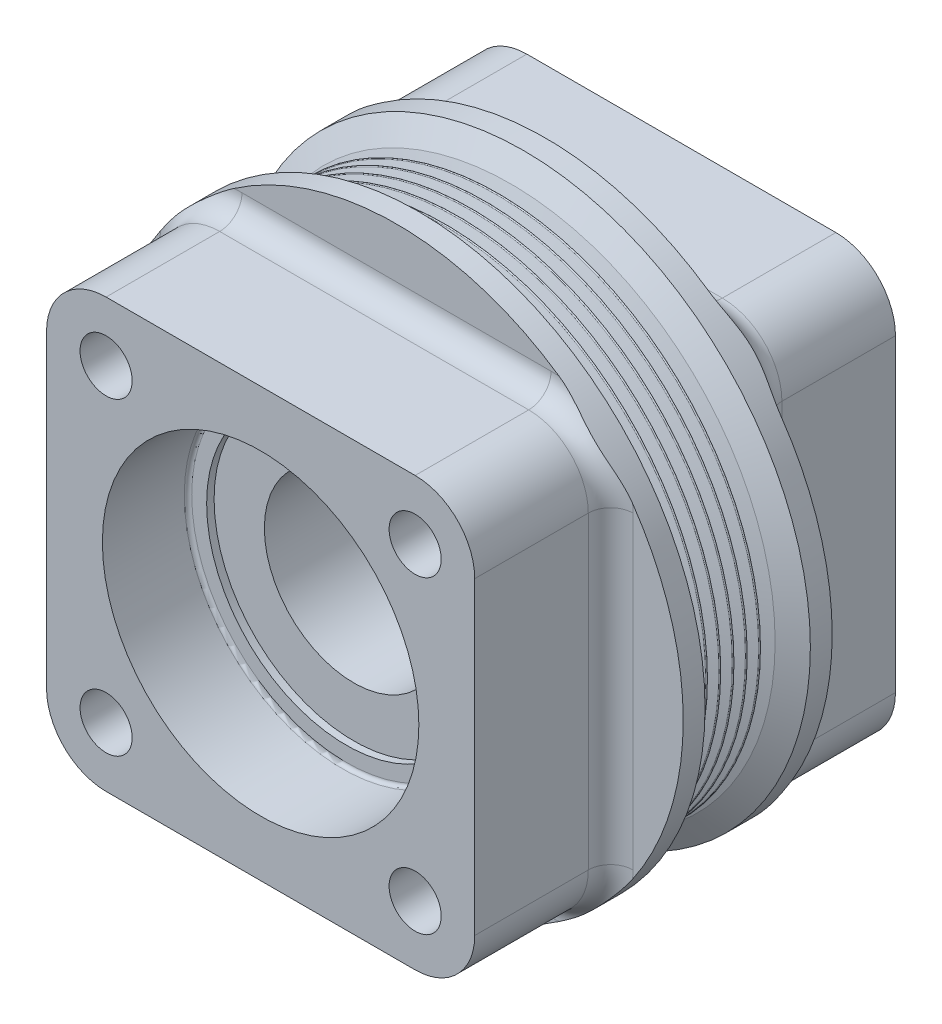
SolidWorks part; units mm, degrees
material "AISI 4340 Aço recozido"
ref_plane "Plano frontal" through (0, 0, 0) normal (0, 0, 1) x (1, 0, 0)
ref_plane "Plano superior" through (0, 0, 0) normal (0, 1, 0) x (1, 0, 0)
ref_plane "Plano direito" through (0, 0, 0) normal (1, 0, 0) x (0, 0, -1)
sketch "Esboço2" plane through (0, 0, 0) normal (0, 0, 1) x (1, 0, 0)
  line L1 (-41.5, -57.5) -> (41.5, -57.5)
  line L2 (-57.5, -41.5) -> (-57.5, 41.5)
  line L3 (-41.5, 57.5) -> (41.5, 57.5)
  line L4 (57.5, -41.5) -> (57.5, 41.5)
  line L5 (-57.5, -57.5) -> (57.5, 57.5) construction
  line L6 (-57.5, 57.5) -> (57.5, -57.5) construction
  arc A0 (-41.5, -57.5) -> (-57.5, -41.5) centre (-41.5, -41.5) cw
  arc A1 (41.5, -57.5) -> (57.5, -41.5) centre (41.5, -41.5) ccw
  arc A2 (41.5, 57.5) -> (57.5, 41.5) centre (41.5, 41.5) cw
  arc A3 (-57.5, 41.5) -> (-41.5, 57.5) centre (-41.5, 41.5) cw
  circle A4 centre (0, 0) radius 42.5
  circle A5 centre (0, 0) radius 25
  point P0 (0, 0)
  dimension "D2" = 16
  dimension "D3" = 85
  dimension "D4" = 50
  dimension "D1" = 115
sketch "Esboço3" plane through (0, 0, 0) normal (1, 0, 0) x (0, 0, -1)
  line L0 (20, 0) -> (20, 77)
  line L1 (20, 77) -> (14.1441, 77)
  line L3 (8.4302, 67.4004) -> (7.3549, 70.3546)
  line L4 (6.8851, 70.3546) -> (5.8098, 67.4004)
  line L5 (4.8702, 67.4004) -> (3.7949, 70.3546)
  line L6 (3.3251, 70.3546) -> (2.2498, 67.4004)
  line L7 (1.3102, 67.4004) -> (0.2349, 70.3546)
  line L8 (-0.2349, 70.3546) -> (-1.3102, 67.4004)
  line L9 (-2.2498, 67.4004) -> (-3.3251, 70.3546)
  line L10 (-3.7949, 70.3546) -> (-4.8702, 67.4004)
  line L11 (-5.8098, 67.4004) -> (-6.8851, 70.3546)
  line L12 (-7.3549, 70.3546) -> (-8.4302, 67.4004)
  line L14 (-14.1441, 77) -> (-20, 77)
  line L15 (-20, 77) -> (-20, 0)
  line L16 (-20, 0) -> (20, 0)
  line L17 (-10.68, 71) -> (10.68, 71) construction
  line L18 (-20, 77) -> (-20, 200)
  line L19 (0, 0) -> (51.063, 0) construction
  line L20 (-9.3698, 67.4004) -> (-10.68, 71)
  line L21 (-10.68, 71) -> (-14.1441, 77)
  line L22 (9.3698, 67.4004) -> (10.68, 71)
  line L23 (10.68, 71) -> (14.1441, 77)
  line L24 (-20, 200) -> (20, 200)
  line L25 (14.1441, 77) -> (20, 87.1427)
  line L26 (20, 87.1427) -> (20, 77)
  line L27 (-14.1441, 77) -> (-20, 87.1427)
  line L28 (-20, 87.1427) -> (-20, 77)
  line L29 (20, 200) -> (20, 77)
  line L30 (20, 77) -> (75, 77)
  line L31 (75, 77) -> (75, 127)
  line L32 (75, 127) -> (-75, 127)
  line L33 (-75, 127) -> (-75, 77)
  line L34 (-75, 77) -> (-20, 77)
  arc A0 (-6.8851, 70.3546) -> (-7.3549, 70.3546) centre (-7.12, 70.269) ccw
  arc A1 (-3.3251, 70.3546) -> (-3.7949, 70.3546) centre (-3.56, 70.269) ccw
  arc A2 (0.2349, 70.3546) -> (-0.2349, 70.3546) centre (0, 70.269) ccw
  arc A3 (3.7949, 70.3546) -> (3.3251, 70.3546) centre (3.56, 70.269) ccw
  arc A4 (7.3549, 70.3546) -> (6.8851, 70.3546) centre (7.12, 70.269) ccw
  arc A5 (9.3698, 67.4004) -> (8.4302, 67.4004) centre (8.9, 67.5714) cw
  arc A6 (5.8098, 67.4004) -> (4.8702, 67.4004) centre (5.34, 67.5714) cw
  arc A7 (2.2498, 67.4004) -> (1.3102, 67.4004) centre (1.78, 67.5714) cw
  arc A8 (-1.3102, 67.4004) -> (-2.2498, 67.4004) centre (-1.78, 67.5714) cw
  arc A9 (-4.8702, 67.4004) -> (-5.8098, 67.4004) centre (-5.34, 67.5714) cw
  arc A10 (-8.4302, 67.4004) -> (-9.3698, 67.4004) centre (-8.9, 67.5714) cw
  point P2 (-7.12, 71)
  point P24 (-7.12, 71)
  point P27 (0, 0)
  point P32 (0, 127)
  point P36 (-7.12, 71)
  point P39 (-3.56, 71)
  point P42 (0, 71)
  point P45 (3.56, 71)
  point P48 (7.12, 71)
  point P54 (5.34, 66.1095)
  point P57 (1.78, 66.1095)
  point P60 (-1.78, 66.1095)
  point P63 (-5.34, 66.1095)
  dimension "D1" = 0.5
  dimension "D2" = 0.25
  dimension "D3" = 40
  dimension "D4" = 40
  dimension "D5" = 20
  dimension "D6" = 3.56
  dimension "D7" = 60
  dimension "D8" = 30
  dimension "D9" = 142
  dimension "D10" = 6
  dimension "D11" = 200
  dimension "D12" = 150
  dimension "D13" = 50
extrude "EXTRUSÃO QUADRADO" add sketch "Esboço2" along normal mid plane 113 contours L3 A2 L4 A1 L1 A0 L2 A3
revolve "REVOLUÇÃO POLIA" add sketch "Esboço3" angle 360 about L16 region at (0, 36.1147, 0)
revolve "CORTE REVOLUÇÃO POLIA" cut sketch "Esboço3<4>" angle 360 about L19 region at (0, 80.3809, -18.048) region at (0, 102, -47.5) region at (0, 99.8952, 0) region at (0, 80.3809, 18.048) region at (0, 102, 47.5)
sketch "Esboço3<4>" plane through (0, 0, 0) normal (1, 0, 0) x (0, 0, -1) same geometry as "Esboço3"
sketch "Esboço4" plane through (0, 0, 0) normal (0, 0, 1) x (1, 0, 0)
  circle A0 centre (0, 0) radius 24
  circle A1 centre (0, 0) radius 42.5
  circle A2 centre (0, 0) radius 27
  circle A3 centre (0, 0) radius 37.5
  dimension "D1" = 85
  dimension "D2" = 48
  dimension "D3" = 75
  dimension "D4" = 54
extrude "FURO EIXO PASSANTE" cut sketch "Esboço4<5>" against normal through all both and the other way through all contours A0
sketch "Esboço4<5>" plane through (0, 0, 0) normal (0, 0, 1) x (1, 0, 0) same geometry as "Esboço4"
extrude "REBAIXO ROLAMENTO 1" cut sketch "Esboço4" along normal offset from surface (23 mm away) 23 from surface contours A1 up to face at (24, 0, -56.5) starting at face at (24, 0, -56.5)
extrude "REBAIXO ROLAMENTO 2" cut sketch "Esboço4<4>" against normal blind 23 from surface contours A1 starting at face at (24, 0, 56.5)
sketch "Esboço4<4>" plane through (0, 0, 0) normal (0, 0, 1) x (1, 0, 0) same geometry as "Esboço4"
extrude "Corte-extrusão4" cut sketch "Esboço4<6>" against normal blind 2 from surface contours A3 starting at face at (-42.5, 0, 33.5)
sketch "Esboço4<6>" plane through (0, 0, 0) normal (0, 0, 1) x (1, 0, 0) same geometry as "Esboço4"
extrude "Corte-extrusão5" cut sketch "Esboço4<7>" along normal blind 2 from surface contours A3 starting at face at (-42.5, 0, -33.5)
sketch "Esboço4<7>" plane through (0, 0, 0) normal (0, 0, 1) x (1, 0, 0) same geometry as "Esboço4"
hole_wizard "FUROS FIXAÇÃO 1" positions "Esboço7" profile "Esboço8" hole size "M16" standard "ISO"
sketch "Esboço7" plane through (0, 0, -56.5) normal (0, 0, -1) x (-1, 0, 0)
  line L1 (-41.5, -41.5) -> (41.5, -41.5)
  line L2 (-41.5, -41.5) -> (-41.5, 41.5)
  line L3 (-41.5, 41.5) -> (41.5, 41.5)
  line L4 (41.5, -41.5) -> (41.5, 41.5)
  line L5 (-41.5, -41.5) -> (41.5, 41.5) construction
  line L6 (-41.5, 41.5) -> (41.5, -41.5) construction
  point P18 (41.5, 41.5)
  point P83 (-41.5, -41.5)
  point P84 (-41.5, 41.5)
  point P85 (41.5, -41.5)
  dimension "D1" = 83
sketch "Esboço8" plane through (-41.5, 41.5, -56.5) normal (1, 0, 0) x (0, 1, 0)
  line L0 (0, 0) -> (0, 34.206)
  line L1 (0, 34.206) -> (7, 30)
  line L2 (7, 30) -> (7, 0)
  line L5 (7, 0) -> (0, 0)
  line L10 (0, 34.206) -> (-7, 30) construction
  line L11 (0, -6.35) -> (0, 107.95) construction
  dimension "Hole Dia." = 14
  dimension "Hole Depth" = 30
  dimension "Drill Angle" = 118
hole_wizard "FUROS FIXAÇÃO 2" positions "Esboço10" profile "Esboço11" hole size "M16" standard "ISO"
sketch "Esboço10" plane through (0, 0, 56.5) normal (0, 0, 1) x (1, 0, 0)
  point P0 (-41.5, 41.5)
  point P3 (41.5, 41.5)
  point P6 (41.5, -41.5)
  point P9 (-41.5, -41.5)
sketch "Esboço11" plane through (-41.5, 41.5, 56.5) normal (1, 0, 0) x (0, -1, 0)
  line L0 (0, 0) -> (0, 34.206)
  line L1 (0, 34.206) -> (7, 30)
  line L2 (7, 30) -> (7, 0)
  line L5 (7, 0) -> (0, 0)
  line L10 (0, 34.206) -> (-7, 30) construction
  line L11 (0, -6.35) -> (0, 107.95) construction
  dimension "Hole Dia." = 14
  dimension "Hole Depth" = 30
  dimension "Drill Angle" = 118
fillet "FILETE ALÍVIO" radius 6 16 edges at (52.8137, 52.8137, 20) (52.8137, -52.8137, 20) (-52.8137, 52.8137, 20) (-52.8137, -52.8137, 20) (57.5, 0, 20) (0, 57.5, 20) (-57.5, 0, 20) (0, -57.5, 20) (-52.8137, -52.8137, -20) (-52.8137, 52.8137, -20) (52.8137, -52.8137, -20) (52.8137, 52.8137, -20) (-57.5, 0, -20) (0, -57.5, -20) (57.5, 0, -20) (0, 57.5, -20)
fillet "Filete4" radius 1 2 edges at (-42.5, 0, -33.5) (-42.5, 0, 33.5)
equation "\"arma-espessura\"= 50                                                                    'disco arma - espessura disco arma"
equation "\"rolamento_D-ext\"= 85               'rolamento arma - diametro externo"
equation "\"rolamento_d-int\"= 45               'rolamento arma - diametro interno"
equation "\"rolamento_b-esp\"= 23               'rolamento arma - espessura"
equation "\"eixo_diam\"= \"rolamento_d-int\"      'eixo arma - diametro"
equation "\"camisa_largura\"=115                                                        'camisa arma - tamanho do lado"
equation "\"camisa_raio\"= 16                                                           'camisa arma - raio canto interno"
equation "\"D1@Esboço2\"=\"camisa_largura\""
equation "\"D2@Esboço2\"=\"camisa_raio\""
equation "\"D3@Esboço2\"=\"rolamento_D-ext\""
equation "\"D4@Esboço2\"=5+\"eixo_diam\""
equation "\"D1\"= \"rolamento_b-esp\" +  ( \"arma-espessura\" - \"rolamento_b-esp\" )  / 2"
equation "\"polia_diam_eff\"= 142"
equation "\"D9@Esboço3\"=\"polia_diam_eff\""
equation "\"escala\"= 1                        'projeto - escala geral"
equation "\"escala_disco-arma\"= 3                                                                  'disco arma - escala geometria disco arma"
equation "\"arma_eixo-furo_folga\"= 4                                                              'disco arma - folga entre furo arma e eixo"
equation "\"arma_rebaixo-camisa_raio\"= 12                                                         'disco arma - raio do rebaixo da camisa da arma "
equation "\"arma_rebaixo-camisa_b\"= \"rolamento_b-esp\" + (\"arma-espessura\"-\"rolamento_b-esp\")/2     'disco arma - profundidade rebaixo camisa"
equation "\"camisa_rebaixo_rolamento\"= 1 * \"rolamento_b-esp\""
equation "\"D1@EXTRUSÃO QUADRADO\" = \"camisa_comprimento-centro\""
equation "\"polia_espessura\"= 40  "
equation "\"D3@Esboço3\"=\"polia_espessura\""
equation "\"D1@Esboço4\"=\"rolamento_D-ext\""
equation "\"D2@Esboço4\"=\"rolamento_d-int\"+3"
equation "\"camisa_comprimento-centro\"= 2*(\"arma_rebaixo-camisa_b\")+\"polia_espessura\" "
equation "\"D1@REBAIXO ROLAMENTO 1\" = \"rolamento_b-esp\""
equation "\"D1@REBAIXO ROLAMENTO 2\" = \"camisa_rebaixo_rolamento\""
equation "\"camisa_furos_dist\"= 83"
equation "\"D1@Esboço7\"=\"camisa_furos_dist\""
equation "\"rolamento_D1-ext\"= 75             'rolamento arma - ressalto diam externo"
equation "\"rolamenot_d2-int\"= 54             'rolamento arma - ressalto diam interno"
equation "\"camisa_furos_prof\"= 30"
equation "\"camisa_raio-alivio\"= 6                                                    'camisa arma - raio de alivio de tensoes no encaixe da arma"
equation "\"D1@FILETE ALÍVIO\" = \"camisa_raio-alivio\""
equation "\"D3@Esboço4\"=\"rolamento_D1-ext\""
equation "\"D4@Esboço4\"=\"rolamenot_d2-int\""
